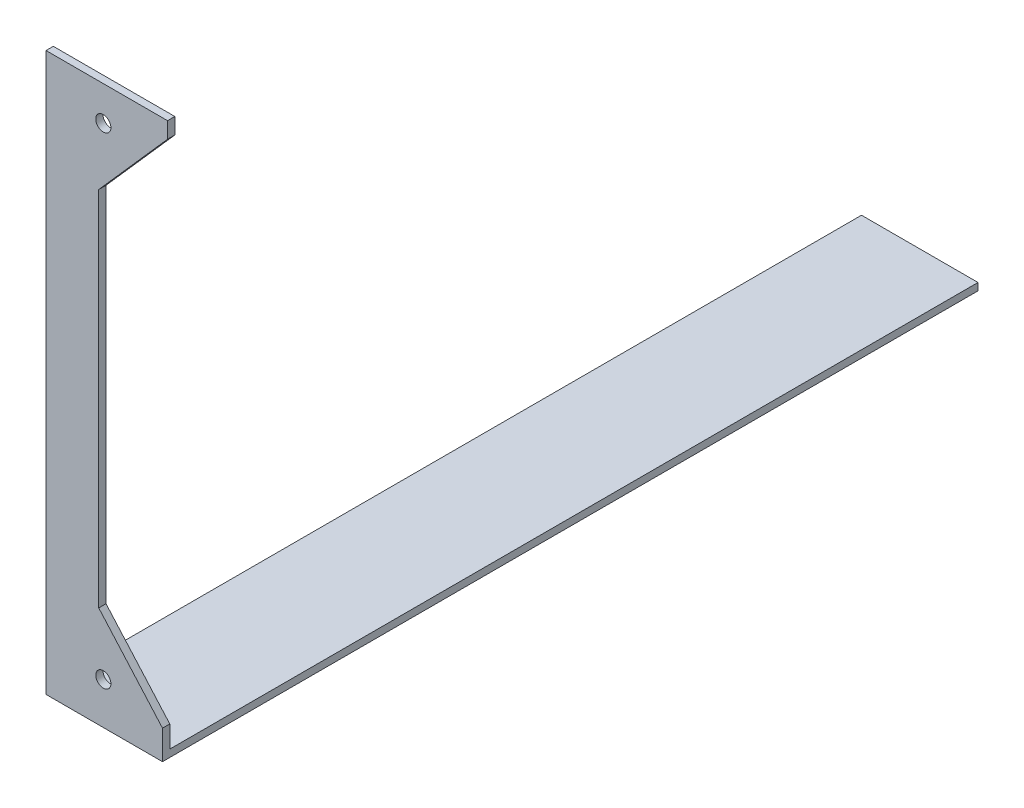
SolidWorks part; units mm, degrees
ref_plane "Front Plane" through (0, 0, 0) normal (0, 0, 1) x (1, 0, 0)
ref_plane "Top Plane" through (0, 0, 0) normal (0, 1, 0) x (1, 0, 0)
ref_plane "Right Plane" through (0, 0, 0) normal (1, 0, 0) x (0, 0, -1)
sketch "Sketch1" plane through (0, 0, 0) normal (0, 0, 1) x (1, 0, 0)
  line L0 (-250, 120) -> (0, 120) construction
  line L1 (-238.5, 99.5) -> (-223.5, 116.5) construction
  line L2 (-244.6, 99.5) -> (-238.5, 99.5) construction
  line L3 (-244.6, 20.5) -> (-244.6, 99.5) construction
  line L4 (-250, 2) -> (-250, 118) construction
  line L5 (0, 0) -> (-250, 0) construction
  line L6 (-238.5, 20.5) -> (-244.6, 20.5) construction
  line L7 (-223.5, 3.5) -> (-238.5, 20.5) construction
  line L8 (-250, 120) -> (-223.5, 120)
  line L9 (-238.5, 99.5) -> (-223.5, 116.5)
  line L10 (-244.6, 99.5) -> (-238.5, 99.5)
  line L11 (-244.6, 20.5) -> (-244.6, 99.5)
  line L12 (-250, 0) -> (-250, 120)
  line L13 (-223.5, 0) -> (-250, 0)
  line L14 (-238.5, 20.5) -> (-244.6, 20.5)
  line L15 (-223.5, 3.5) -> (-238.5, 20.5)
  line L16 (-223.5, 116.5) -> (-223.5, 120)
  line L17 (-223.5, 3.5) -> (-223.5, 0)
  line L18 (-238.5, 20.5) -> (-238.5, 99.5)
  line L19 (-224.6, 4.7467) -> (-224.6, 0)
  arc A0 (-239.15, 112.5) -> (-235.85, 112.5) centre (-237.5, 112.5) ccw construction
  arc A1 (-235.85, 112.5) -> (-239.15, 112.5) centre (-237.5, 112.5) ccw construction
  arc A2 (-235.85, 7.5) -> (-239.15, 7.5) centre (-237.5, 7.5) ccw construction
  arc A3 (-239.15, 7.5) -> (-235.85, 7.5) centre (-237.5, 7.5) ccw construction
  arc A4 (-239.15, 112.5) -> (-235.85, 112.5) centre (-237.5, 112.5) ccw
  arc A5 (-235.85, 112.5) -> (-239.15, 112.5) centre (-237.5, 112.5) ccw
  arc A6 (-235.85, 7.5) -> (-239.15, 7.5) centre (-237.5, 7.5) ccw
  arc A7 (-239.15, 7.5) -> (-235.85, 7.5) centre (-237.5, 7.5) ccw
  dimension "D1" = 25.4
extrude "Boss-Extrude1" add sketch "Sketch1" along normal blind 1.5875 contours L14 L18 L10 L11 | L17 L15 L14 L11 L10 L9 L16 L8 L12 L13 A7 A6 A5 A4 region at (-236.75, 118.7711, 0) region at (-241.55, 60, 0)
sketch "Sketch2" plane through (0, 0, 0) normal (0, 1, 0) x (1, 0, 0)
  line L1 (-250, -1.5875) -> (-250, 176.2125)
  line L2 (-250, 176.2125) -> (-224.6, 176.2125)
  line L3 (-224.6, 176.2125) -> (-224.6, -1.5875)
  line L4 (-224.6, -1.5875) -> (-250, -1.5875) construction
  line L5 (-224.6, -1.5875) -> (-250, -1.5875)
  dimension "D1" = 177.8
extrude "Boss-Extrude2" add sketch "Sketch2" against normal blind 1.5875 contours L3 L5 L1 L2
